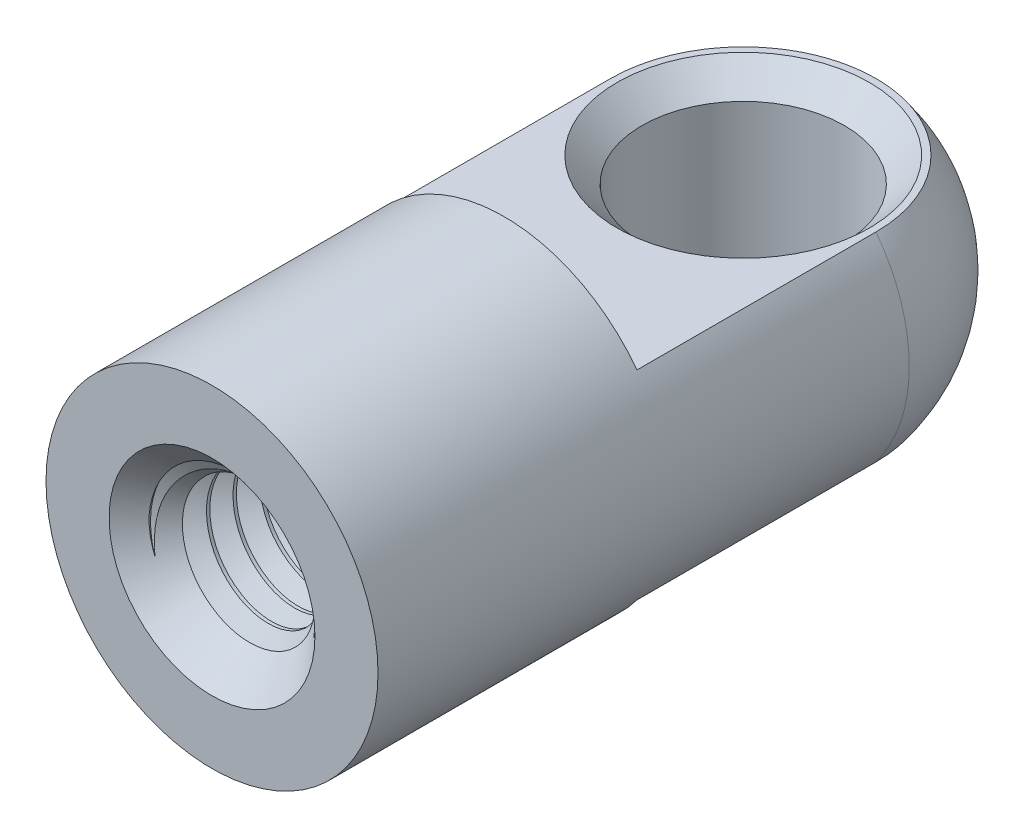
SolidWorks part; units mm, degrees
ref_plane "Front Plane" through (0, 0, 0) normal (0, 0, 1) x (1, 0, 0)
ref_plane "Top Plane" through (0, 0, 0) normal (0, 1, 0) x (1, 0, 0)
ref_plane "Right Plane" through (0, 0, 0) normal (1, 0, 0) x (0, 0, -1)
sketch "Sketch1" plane through (0, 0, 0) normal (0, 1, 0) x (1, 0, 0)
  line L0 (0, 0) -> (0, 16) construction
  line L1 (-5, 0) -> (5, 0) construction
  line L2 (5, 0) -> (5, 16) construction
  line L3 (-2.5, 8) -> (2.5, 8) construction
  line L4 (-2.5, 8) -> (-2.5, 0) construction
  line L6 (2.5, 8) -> (2.5, 0) construction
  circle A0 centre (0, 16) radius 3.05 construction
  circle A1 centre (0, 16) radius 5 construction
  point P5 (0, 0)
  point P6 (0, 8)
  point P9 (0, 21)
  point P13 (0, 8)
  point P14 (0, 12.95)
  point P15 (0, 19.05)
  dimension "ID" = 6.1
  dimension "Overall Diameter" = 10
  dimension "Shank Center Length" = 16
  dimension "Shank Thread Length" = 8
  dimension "Shank Thread Size" = 5
sketch "Sketch2" plane through (0, 0, 0) normal (1, 0, 0) x (0, 0, -1)
  line L0 (21, 3) -> (21, -3) construction
  line L1 (0, 0) -> (16, 0) construction
  line L2 (0, 2.5) -> (0, -2.5) construction
  line L3 (0, 2.5) -> (8, 2.5) construction
  line L4 (8, 2.5) -> (8, -2.5) construction
  line L5 (8, -2.5) -> (0, -2.5) construction
  line L6 (19.05, 3) -> (19.05, -3) construction
  line L7 (12.95, 3) -> (12.95, -3) construction
  point P2 (21, 0)
  point P5 (0.8, 0)
  point P10 (0, 0)
  point P16 (0, -2.5)
  point P20 (19.05, 0)
  point P22 (12.95, 0)
  dimension "Top Width" = 6
  dimension "Shank Thread Pitch" = 0.8
  dimension "D1" = 5
sketch "Sketch3" plane through (0, 0, 0) normal (0, 1, 0) x (1, 0, 0)
  line L0 (0, 8) -> (-2.5, 8)
  line L1 (-2.5, 8) -> (-2.5, 0)
  line L2 (-5, 0) -> (5, 0) construction
  line L3 (-2.5, 0) -> (-5, 0)
  line L4 (-5, 0) -> (-5, 16)
  line L6 (0, 21) -> (0, 8)
  circle A0 centre (0, 16) radius 5 construction
  arc A1 (-5, 16) -> (0, 21) centre (0, 16) cw
revolve "Revolve1" add sketch "Sketch3" angle 360 about L0
sketch "Sketch4" plane through (0, 0, 0) normal (1, 0, 0) x (0, 0, -1)
  line L0 (21, 3) -> (8.8, 3) construction
  line L1 (0, 5) -> (16, 5) construction
  line L3 (21, 3) -> (8.8, 3)
  line L4 (8.8, 3) -> (8.8, 5)
  line L5 (8.8, 5) -> (8.8, 5.8)
  line L6 (8.8, 5.8) -> (21, 5.8)
  line L7 (21, 5.8) -> (21, 3)
  line L8 (0, 0) -> (16, 0) construction
  line L9 (0, 0) -> (16, 0) construction
  line L10 (8.8, -3) -> (8.8, -5) construction
  line L11 (21, -3) -> (8.8, -3) construction
  line L12 (21, -5.8) -> (21, -3)
  line L13 (8.8, -5.8) -> (21, -5.8)
  line L14 (8.8, -5) -> (8.8, -5.8)
  line L15 (8.8, -3) -> (8.8, -5)
  line L16 (21, -3) -> (8.8, -3)
  line L19 (16, 5) -> (16, -5) construction
  line L20 (8, 2.5) -> (8, -2.5) construction
  point P8 (8.8, 3)
  dimension "D2" = 0.8
  dimension "D1" = 0.8
extrude "Cut-Extrude1" cut sketch "Sketch4" against normal through all both and the other way through all
sketch "Sketch5" plane through (0, 0, 0) normal (0, 1, 0) x (1, 0, 0)
  circle A0 centre (0, 16) radius 3.05 construction
  circle A1 centre (0, 16) radius 3.05
extrude "Cut-Extrude2" cut sketch "Sketch5" against normal through all both and the other way through all
chamfer "Chamfer1" distance 0.75 angle 45 2 edges at (0, -3, -12.95) (0, 3, -19.05)
sketch "Sketch9" plane through (0, 0, 0) normal (0, 0, 1) x (1, 0, 0)
  line L0 (2.5, 0) -> (0, 0) construction
  line L1 (0, 0) -> (-2.3492, -0.8551) construction
  circle A0 centre (0, 0) radius 2.5 construction
  circle A1 centre (0, 0) radius 2.5 construction
  point P6 (-2.3492, -0.8551)
  dimension "D1" = 200
sketch "Sketch6" plane through (0, 0, 0) normal (0, 0, 1) x (1, 0, 0)
  circle A0 centre (0, 0) radius 2.5
curve "Helix/Spiral1" pitch 0.8 height 10 radius 2.5 centre (0, 0, 0) axis (0, 0, -1) start towards (0, 1, 0)
sketch "Sketch7" plane through (0, 0, 0) normal (1, 0, 0) x (0, 0, -1)
  line L0 (-0.775, 2.5433) -> (0.025, 2.5433) construction
  line L1 (0.025, 2.5433) -> (-0.375, 1.8505) construction
  line L2 (-0.375, 1.8505) -> (-0.775, 2.5433) construction
  line L3 (-0.375, 2.5433) -> (-0.375, 2.4567) construction
  line L4 (-0.375, 2.4567) -> (-0.375, 1.9371) construction
  line L5 (-0.375, 1.9371) -> (-0.375, 1.8505) construction
  line L6 (-0.425, 1.9371) -> (-0.325, 1.9371)
  line L7 (0, 2.5) -> (-0.75, 2.5) construction
  line L9 (-0.025, 2.4567) -> (-0.725, 2.4567) construction
  line L11 (-0.425, 1.9371) -> (-0.325, 1.9371) construction
  line L13 (-0.325, 1.9371) -> (0, 2.5)
  line L14 (0, 2.5) -> (-0.75, 2.5)
  line L15 (-0.75, 2.5) -> (-0.425, 1.9371)
  point P5 (-0.375, 1.9371)
  point P14 (-0.375, 2.4567)
  point P16 (-0.375, 2.5)
  point P17 (-0.375, 2.5)
  dimension "D1" = 0.8
  dimension "D2" = 0.1
sweep "Sweep2" add profiles "Sketch7" path "Helix/Spiral1"
sketch "Sketch8" plane through (0, 0, 0) normal (0, 0, 1) x (1, 0, 0)
  circle A0 centre (0, 0) radius 3.1
  dimension "D1" = 6.2
extrude "Cut-Extrude3" cut sketch "Sketch8" against normal blind 10 draft 45 and the other way through all
equation "\"D2@Sketch4\"=\"D1@Sketch4\""
equation "\"D3@Helix/Spiral1\" = \"Shank Thread Length@Sketch1\" * 1.25"
equation "\"D4@Helix/Spiral1\" = \"Shank Thread Pitch@Sketch2\""
equation "\"D1@Sketch7\" = \"Shank Thread Pitch@Sketch2\""
equation "\"D2@Sketch7\"=\"D1@Sketch7\"/8"
equation "\"D1@Sketch8\" = \"Shank Thread Size@Sketch1\" + 1.5 * \"Shank Thread Pitch@Sketch2\""
equation "\"D1@Sketch2\" = \"Shank Thread Size@Sketch1\""
equation "\"D1@Sketch4\"=\"Shank Center Length@Sketch1\"*.05"
